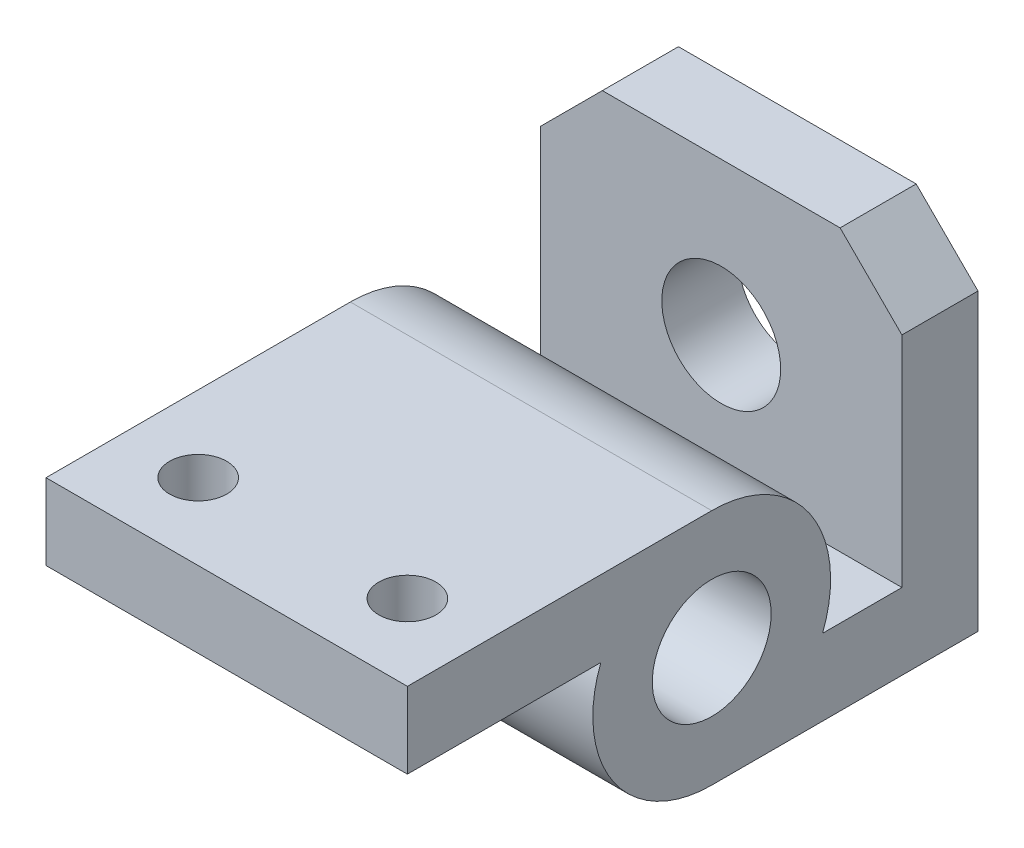
SolidWorks part; units mm, degrees
ref_plane "Front Plane" through (0, 0, 0) normal (0, 0, 1) x (1, 0, 0)
ref_plane "Top Plane" through (0, 0, 0) normal (0, 1, 0) x (1, 0, 0)
ref_plane "Right Plane" through (0, 0, 0) normal (1, 0, 0) x (0, 0, -1)
sketch "Sketch1" plane through (0, 0, 0) normal (1, 0, 0) x (0, 0, -1)
  line L0 (0, -25) -> (56, -25)
  line L1 (56, -25) -> (56, 50)
  line L2 (56, 50) -> (40, 50)
  line L3 (40, 50) -> (40, -9)
  line L4 (40, -9) -> (23.3238, -9)
  line L5 (0, 25) -> (-64, 25)
  line L6 (-64, 25) -> (-64, 9)
  line L7 (-64, 9) -> (-23.3238, 9)
  arc A0 (-23.3238, 9) -> (0, -25) centre (0, 0) ccw
  circle A1 centre (0, 0) radius 12.5
  arc A2 (23.3238, -9) -> (0, 25) centre (0, 0) ccw
  dimension "D4" = 25
  dimension "D5" = 50
  dimension "D1" = 16
  dimension "D2" = 16
  dimension "D3" = 16
  dimension "D6" = 64
  dimension "D7" = 56
  dimension "D8" = 75
extrude "Boss-Extrude1" add sketch "Sketch1" along normal mid plane 76 contours L5 L6 L7 A0 L0 L1 L2 L3 L4 A2
extrude "Cut-Extrude1" cut sketch "Sketch1<3>" against normal through all both and the other way through all contours A1
sketch "Sketch1<3>" plane through (0, 0, 0) normal (1, 0, 0) x (0, 0, -1) same geometry as "Sketch1"
chamfer "Chamfer1" distance 13 distance2 13 2 edges at (-38, 50, -48) (38, 50, -48)
sketch "Sketch3" plane through (0, 0, -40) normal (0, 0, 1) x (1, 0, 0)
  line L0 (25, 50) -> (-25, 50) construction
  line L1 (-38, 37) -> (-38, -9) construction
  circle A0 centre (0, 18) radius 12.5
  dimension "D1" = 25
  dimension "D2" = 32
  dimension "D3" = 38
extrude "Cut-Extrude3" cut sketch "Sketch3" against normal blind 76 contours A0
sketch "Sketch4" plane through (0, 25, 0) normal (0, 1, 0) x (1, 0, 0)
  line L0 (0, 0) -> (0, -76.1945) construction
  line L1 (-43.3167, -48) -> (57.2997, -48) construction
  line L2 (38, -64) -> (-38, -64) construction
  circle A0 centre (-22, -48) radius 6
  circle A1 centre (22, -48) radius 6
  dimension "D2" = 12
  dimension "D1" = 16
  dimension "D3" = 44
extrude "Cut-Extrude4" cut sketch "Sketch4" against normal through all
